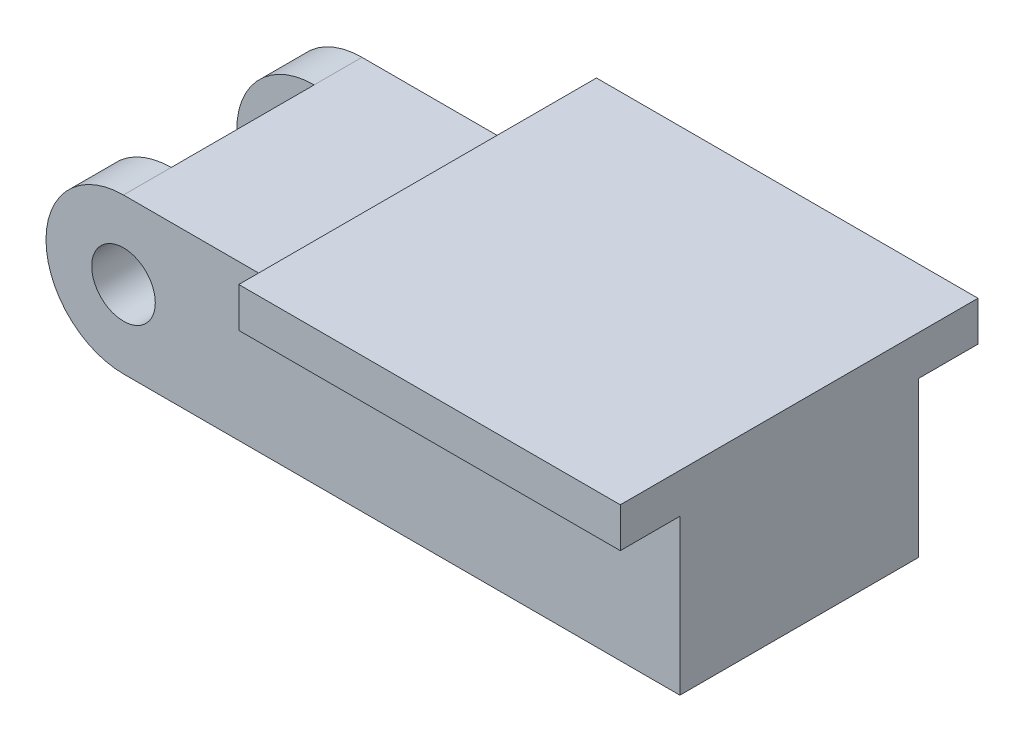
SolidWorks part; units mm, degrees
ref_plane "Front Plane" through (0, 0, 0) normal (0, 0, 1) x (1, 0, 0)
ref_plane "Top Plane" through (0, 0, 0) normal (0, 1, 0) x (1, 0, 0)
ref_plane "Right Plane" through (0, 0, 0) normal (1, 0, 0) x (0, 0, -1)
sketch "Sketch1" plane through (0, 0, 0) normal (1, 0, 0) x (0, 0, -1)
  line L1 (-15, 0) -> (15, 0)
  line L2 (-15, 0) -> (-15, 19.5)
  line L3 (-15, 19.5) -> (15, 19.5)
  line L4 (15, 0) -> (15, 19.5)
  point P4 (0, 0)
  dimension "D1" = 30
  dimension "D2" = 19.5
extrude "Boss-Extrude1" add sketch "Sketch1" against normal blind 70
sketch "Sketch6" plane through (0, 0, 15) normal (0, 0, 1) x (1, 0, 0)
  line L0 (-70, 19.5) -> (-70, 0) construction
  line L1 (-70, 19.5) -> (-70, 0)
  arc A0 (-70, 19.5) -> (-70, 0) centre (-70, 9.75) ccw
extrude "Boss-Extrude2" add sketch "Sketch6" against normal up to surface (30 mm away) up to face at (-35, 9.75, -15)
sketch "Sketch7" plane through (0, 19.5, 0) normal (0, 1, 0) x (1, 0, 0)
  line L1 (-48, 22.5) -> (0, 22.5)
  line L2 (-48, 22.5) -> (-48, -22.5)
  line L3 (-48, -22.5) -> (0, -22.5)
  line L4 (0, 22.5) -> (0, -22.5)
  point P4 (0, 0)
  dimension "D1" = 48
  dimension "D2" = 45
extrude "Boss-Extrude3" add sketch "Sketch7" along normal blind 5
sketch "Sketch8" plane through (0, 0, 15) normal (0, 0, 1) x (1, 0, 0)
  line L0 (-70, 19.5) -> (-70, 0) construction
  circle A0 centre (-70, 9.75) radius 9.75
extrude "Cut-Extrude2" cut sketch "Sketch8" against normal offset from surface (18 mm away) 6 from offset 6 up to face at (-39.55, 11.7, -15) offset against normal yes
sketch "Sketch9" plane through (0, 0, 15) normal (0, 0, 1) x (1, 0, 0)
  line L0 (-70, 19.5) -> (-70, 0) construction
  circle A0 centre (-70, 9.75) radius 4
  dimension "D1" = 8
extrude "Cut-Extrude3" cut sketch "Sketch9" against normal through all
sketch "Sketch10" plane through (0, 0, 0) normal (0, -1, 0) x (1, 0, 0)
  line L0 (0, 0) -> (-49.6118, 0) construction
  line L2 (-48, 22.5) -> (0, 22.5) construction
  line L3 (-24, 22.5) -> (-24, -11.6735) construction
  circle A0 centre (-24, 0) radius 9
  point P11 (0, 0)
  dimension "D1" = 18
extrude "Cut-Extrude4" cut sketch "Sketch10" against normal blind 10
